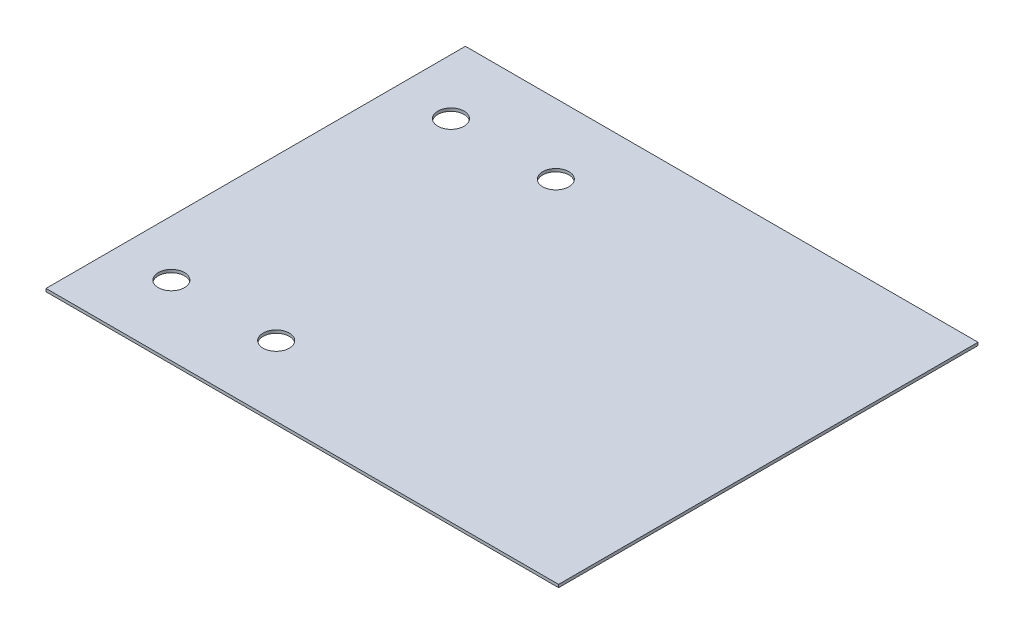
SolidWorks part; units mm, degrees
ref_plane "Front Plane" through (0, 0, 0) normal (0, 0, 1) x (1, 0, 0)
ref_plane "Top Plane" through (0, 0, 0) normal (0, 1, 0) x (1, 0, 0)
ref_plane "Right Plane" through (0, 0, 0) normal (1, 0, 0) x (0, 0, -1)
sketch "Sketch1" plane through (0, 0, 0) normal (0, 1, 0) x (1, 0, 0)
  line L1 (0, 0) -> (558.8, 0)
  line L2 (0, 0) -> (0, 457.2)
  line L3 (0, 457.2) -> (558.8, 457.2)
  line L4 (558.8, 0) -> (558.8, 457.2)
  dimension "D1" = 558.8
  dimension "D2" = 457.2
extrude "Boss-Extrude1" add sketch "Sketch1" along normal blind 3.175
sketch "Sketch2" plane through (0, 3.175, 0) normal (0, 1, 0) x (1, 0, 0)
  line L1 (60.4606, 381) -> (174.7606, 381) construction
  line L2 (558.8, 457.2) -> (0, 457.2) construction
  line L3 (60.4606, 76.2) -> (174.7606, 76.2) construction
  line L4 (0, 0) -> (558.8, 0) construction
  circle A0 centre (60.4606, 381) radius 14.2875
  circle A1 centre (174.7606, 381) radius 14.2875
  circle A2 centre (60.4606, 76.2) radius 14.2875
  circle A3 centre (174.7606, 76.2) radius 14.2875
  dimension "D1" = 28.575
  dimension "D2" = 28.575
  dimension "D3" = 28.575
  dimension "D4" = 28.575
  dimension "D5" = 114.3
  dimension "D6" = 114.3
  dimension "D7" = 76.2
  dimension "D8" = 76.2
extrude "Cut-Extrude1" cut sketch "Sketch2" against normal blind 3.175
